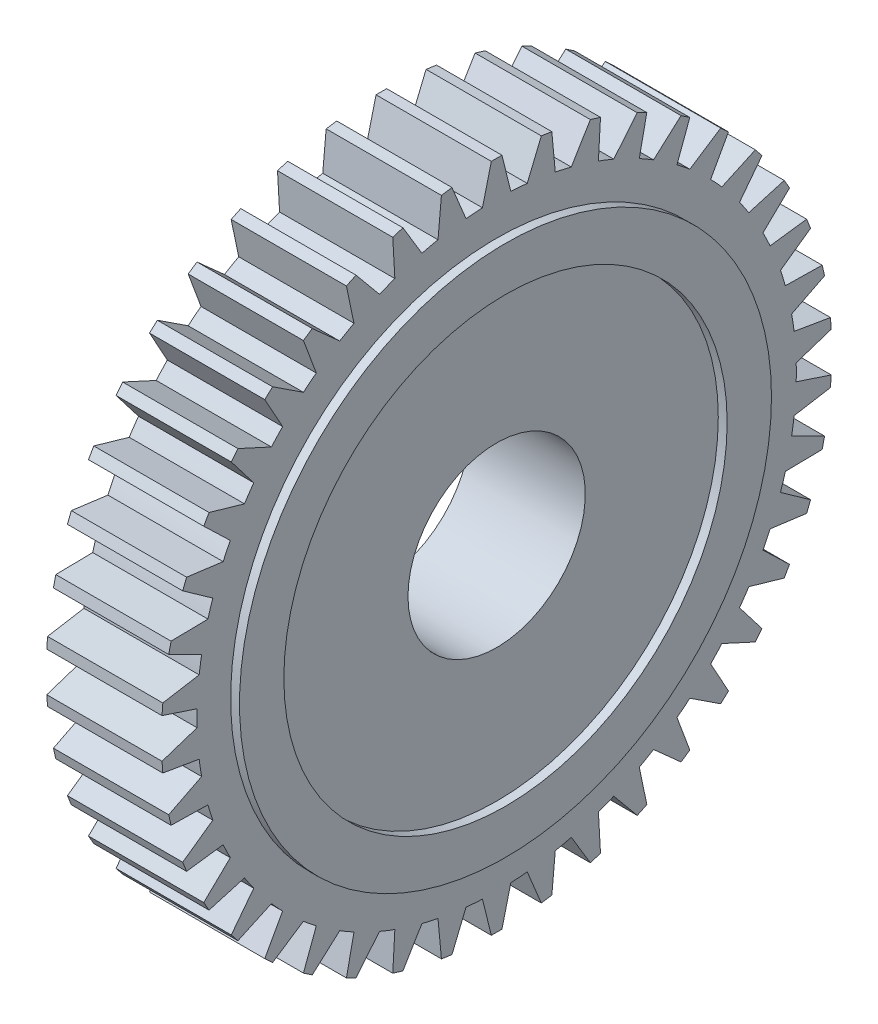
SolidWorks part; units mm, degrees
material "AISI 8620 Steel, carburized"
ref_plane "Front Plane" through (0, 0, 0) normal (1, 0, 0) x (0, 1, 0)
ref_plane "Top Plane" through (0, 0, 0) normal (0, 0, 1) x (0, 1, 0)
ref_plane "Right Plane" through (0, 0, 0) normal (0, 1, 0) x (-1, 0, 0)
sketch "Sketch1" plane through (0, 0, 0) normal (1, 0, 0) x (0, 1, 0)
  line L0 (-48.2579, 0) -> (43.496, 0) construction
  line L1 (-37.8, 0.6) -> (-37.8, -0.6)
  line L2 (-37.8, 0.6) -> (-33.7621, 1.5993)
  line L3 (-37.8, -0.6) -> (-33.7621, -1.5993)
  line L4 (-37.8, -0.6) -> (-37.8, 2.4856) construction
  circle A0 centre (0, 0) radius 10
  circle A1 centre (0, 0) radius 30
  circle A2 centre (0, 0) radius 25
  circle A3 centre (0, 0) radius 33.8
  point P6 (0, 0)
  point P12 (-37.8, 0)
  point P13 (37.8, 0)
  dimension "D1" = 20
  dimension "D2" = 60
  dimension "D3" = 50
  dimension "D4" = 67.6
  dimension "D5" = 37.8
  dimension "D6" = 1.2
  dimension "D7" = 256.1
extrude "Boss-Extrude1" add sketch "Sketch1" along normal mid plane 13 contours A2 A0 | A1 A2 | A3 A1 region at (0, 0.7772, 32.8348) region at (0, -29.1515, 0) region at (0, -24.2929, 0)
extrude "Boss-Extrude2" add sketch "Sketch1<3>" along normal mid plane 15 contours A1 A2 region at (0, -29.1515, 0)
sketch "Sketch1<3>" plane through (0, 0, 0) normal (1, 0, 0) x (0, 1, 0) same geometry as "Sketch1"
extrude "Boss-Extrude3" add sketch "Sketch1<4>" along normal mid plane 13 contours A3 L2 L1 L3 region at (0, -35.4909, 0)
sketch "Sketch1<4>" plane through (0, 0, 0) normal (1, 0, 0) x (0, 1, 0) same geometry as "Sketch1"
pattern_circular "CirPattern1" count 42 over 360 about axis through (6.5, 0, 0) along (1, 0, 0) of "Boss-Extrude3"
ref_axis "Axis1" through (0, 0, 41.5131) along (0, 0, -1)
ref_axis "Axis2" through (6.5, 0, 0) along (-1, 0, 0)
